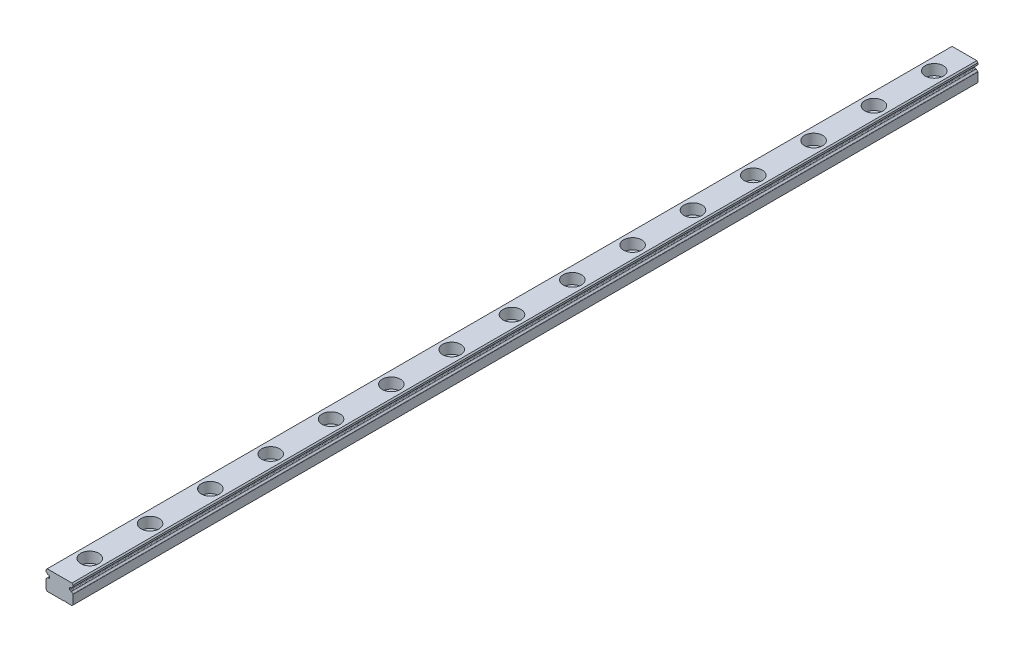
SolidWorks part; units mm, degrees
ref_plane "Front Plane" through (0, 0, 0) normal (0, 0, 1) x (1, 0, 0)
ref_plane "Top Plane" through (0, 0, 0) normal (0, 1, 0) x (1, 0, 0)
ref_plane "Right Plane" through (0, 0, 0) normal (1, 0, 0) x (0, 0, -1)
sketch "Sketch1" plane through (0, 0, 0) normal (0, 0, 1) x (1, 0, 0)
  line L0 (-4.5, 0) -> (4.5, 0) construction
  line L1 (0, -3.25) -> (0, 3.25) construction
  line L2 (0, 3.25) -> (0, -3.25) construction
  line L3 (-3, 3.25) -> (3, 3.25) construction
  line L4 (-1.75, -0.25) -> (1.75, -0.25) construction
  point P0 (0, -0.25)
  point P3 (-4.5, -3.25)
  point P4 (0, 0)
  point P8 (0, 0)
  point P11 (0, 3.25)
  point P15 (0, 3.25)
  point P17 (0, -0.25)
  point P18 (4.5, 3.25)
  point P20 (-4.5, 3.25)
  dimension "Rail Width" = 9
  dimension "Rail Height" = 6.5
  dimension "Mounting Hole Depth" = 3
  dimension "Mounting Hole Counterbore Diameter" = 6
  dimension "Mounting Hole Diameter" = 3.5
sketch "Sketch2" plane through (0, 0, 0) normal (1, 0, 0) x (0, 0, -1)
  line L0 (150, 0) -> (-150, 0) construction
  line L1 (-9.5, 3.25) -> (9.5, 3.25) construction
  line L3 (0, 3.25) -> (0, 0) construction
  point P0 (-140, 0)
  point P4 (0, 0)
  point P5 (-120, 0)
  point P6 (-130, 0)
  point P9 (-140, 3.25)
  point P10 (0, 3.25)
  point P11 (150, 3.25)
  point P13 (-150, 3.25)
  point P14 (130, 0)
  point P17 (-150, -3.25)
  dimension "Rail Length" = 300
  dimension "Mounting Hole Center to Edge" = 10
  dimension "Mounting Hole Center to Center" = 20
  dimension "Number of Mounting Holes" = 19
  dimension "Break Line" = 10
sketch "Sketch3" plane through (0, 0, 0) normal (0, 0, 1) x (1, 0, 0)
  point P0 (0, 3.25)
  line B0 (-4.5, 0.1917) -> (-4.5, -2.85)
  line B1 (-4.5, -2.85) -> (-4.1, -3.25)
  line B2 (-4.1, -3.25) -> (1.4, -3.25)
  line B3 (2.2, -3.25) -> (4.1, -3.25)
  line B4 (4.1, -3.25) -> (4.5, -2.85)
  line B5 (4.5, -2.85) -> (4.5, 0.1917)
  line B6 (3.8235, 0.8135) -> (3.4826, 0.8434)
  line B7 (3.3, 1.0426) -> (3.3, 1.4574)
  line B8 (3.4826, 1.6566) -> (3.8235, 1.6865)
  line B9 (4.5, 2.3083) -> (4.5, 2.85)
  line B10 (4.5, 2.85) -> (4.1, 3.25)
  line B11 (4.1, 3.25) -> (-4.1, 3.25)
  line B12 (-4.1, 3.25) -> (-4.5, 2.85)
  line B13 (-4.5, 2.85) -> (-4.5, 2.3083)
  line B14 (-3.8235, 1.6865) -> (-3.4826, 1.6566)
  line B15 (-3.3, 1.4574) -> (-3.3, 1.0426)
  line B16 (-3.4826, 0.8434) -> (-3.8235, 0.8135)
  arc B17 (2.2, -3.25) -> (1.4, -3.25) centre (1.8, -3.55) ccw
  arc B18 (4.5, 0.1917) -> (4.4087, 0.3297) centre (4.35, 0.1917) ccw
  arc B19 (3.9395, 0.7405) -> (4.4087, 0.3297) centre (4.8, 1.25) ccw
  arc B20 (3.9395, 0.7405) -> (3.8235, 0.8135) centre (3.8104, 0.6641) ccw
  arc B21 (3.3, 1.0426) -> (3.4826, 0.8434) centre (3.5, 1.0426) ccw
  arc B22 (3.4826, 1.6566) -> (3.3, 1.4574) centre (3.5, 1.4574) ccw
  arc B23 (3.8235, 1.6865) -> (3.9395, 1.7595) centre (3.8104, 1.8359) ccw
  arc B24 (4.4087, 2.1703) -> (3.9395, 1.7595) centre (4.8, 1.25) ccw
  arc B25 (4.4087, 2.1703) -> (4.5, 2.3083) centre (4.35, 2.3083) ccw
  arc B26 (-4.5, 2.3083) -> (-4.4087, 2.1703) centre (-4.35, 2.3083) ccw
  arc B27 (-3.9395, 1.7595) -> (-4.4087, 2.1703) centre (-4.8, 1.25) ccw
  arc B28 (-3.9395, 1.7595) -> (-3.8235, 1.6865) centre (-3.8104, 1.8359) ccw
  arc B29 (-3.3, 1.4574) -> (-3.4826, 1.6566) centre (-3.5, 1.4574) ccw
  arc B30 (-3.4826, 0.8434) -> (-3.3, 1.0426) centre (-3.5, 1.0426) ccw
  arc B31 (-3.8235, 0.8135) -> (-3.9395, 0.7405) centre (-3.8104, 0.6641) ccw
  arc B32 (-4.4087, 0.3297) -> (-3.9395, 0.7405) centre (-4.8, 1.25) ccw
  arc B33 (-4.4087, 0.3297) -> (-4.5, 0.1917) centre (-4.35, 0.1917) ccw
sketch_block_instance "9mm Block-1"
sketch_block "9mm Block"
extrude "Boss-Extrude1" add sketch "Sketch3" against normal up to vertex (150 mm away) from vertex up to point (0, 0, -150) starting at point (0, 0, 150)
ref_plane "Plane1" through (0, 0, 140) normal (0, 0, 1) x (1, 0, 0)
sketch "Sketch4" plane through (0, 0, 140) normal (0, 0, 1) x (1, 0, 0)
  line L0 (0, 3.25) -> (0, -3.25)
  line L1 (0, -3.25) -> (-1.75, -3.25)
  line L3 (-1.75, -3.25) -> (-1.75, -0.25)
  line L4 (-1.75, -0.25) -> (-3, -0.25)
  line L5 (-3, -0.25) -> (-3, 3.25)
  line L6 (-3, 3.25) -> (0, 3.25)
  point P6 (-1.75, -0.25)
revolve "Cut-Revolve1" cut sketch "Sketch4" angle 360 about L0
sketch "Sketch6" plane through (0, 0, 0) normal (1, 0, 0) x (0, 0, -1)
  line L0 (-137, -0.25) -> (-143, -0.25) construction
  line L5 (-137, -0.25) -> (-143, -0.25)
  line L17 (-141.75, -0.25) -> (-141.75, -3.25) construction
  line L18 (-138.25, -3.25) -> (-138.25, -0.25) construction
  line L32 (-137, -0.25) -> (-137, 3.25) construction
  line L33 (-143, 3.25) -> (-143, -0.25) construction
  line L34 (-141.75, -0.25) -> (-141.75, -3.25)
  line L35 (-138.25, -3.25) -> (-138.25, -0.25)
  line L36 (-137, -0.25) -> (-137, 3.25)
  line L37 (-143, 3.25) -> (-143, -0.25)
  line L38 (0, 3.25) -> (0, -3.25) construction
  line L40 (143, 3.25) -> (143, -0.25)
  line L41 (137, -0.25) -> (137, 3.25)
  line L42 (138.25, -3.25) -> (138.25, -0.25)
  line L43 (141.75, -0.25) -> (141.75, -3.25)
  line L44 (137, -0.25) -> (143, -0.25)
sketch "Sketch7" plane through (0, 0, 0) normal (0, 0, 1) x (1, 0, 0)
  line L0 (3, -0.25) -> (3, 3.25) construction
  line L1 (-3, 3.25) -> (-3, -0.25) construction
  line L2 (3, -0.25) -> (3, 3.25)
  line L3 (-3, 3.25) -> (-3, -0.25)
  line L4 (1.75, -3.0525) -> (1.75, -0.25) construction
  line L11 (1.75, -3.0525) -> (1.75, -0.25)
  line L18 (-1.75, -0.25) -> (-1.75, -3.25) construction
  line L32 (3, -0.25) -> (-3, -0.25) construction
  line L34 (-1.75, -0.25) -> (-1.75, -3.25)
  line L37 (3, -0.25) -> (-3, -0.25)
pattern_linear "LPattern1" count 15 spacing 20 along (0, 0, -1) of "Cut-Revolve1"
sketch "Sketch8" plane through (0, -3.25, 0) normal (0, -1, 0) x (1, 0, 0)
  point P0 (0, 100)
  point P1 (0, -100)
equation "\"D3@LPattern1\"=\"Mounting Hole Center to Center@Sketch2\""
equation "\"Break Line@Sketch2\"=\"Mounting Hole Center to Center@Sketch2\"/2"
